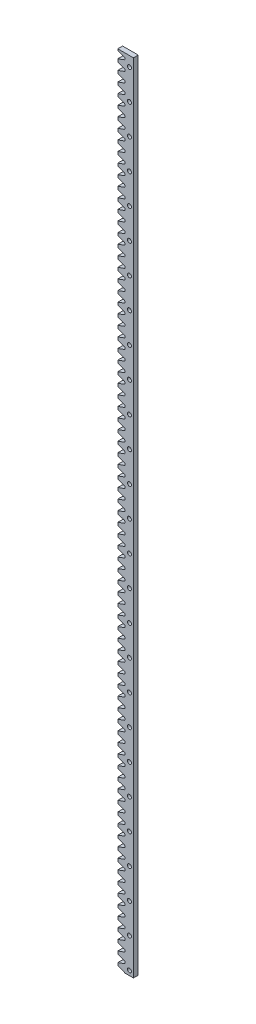
SolidWorks part; units mm, degrees
material "Thornel Mat VMA"
ref_plane "前视基准面" through (0, 0, 0) normal (0, 0, 1) x (1, 0, 0)
ref_plane "上视基准面" through (0, 0, 0) normal (0, 1, 0) x (1, 0, 0)
ref_plane "右视基准面" through (0, 0, 0) normal (1, 0, 0) x (0, 0, -1)
ref_axis "基准轴1" through (0, -55, 0) along (0, 1, 0)
sketch "SketchCI.m_strSketchName" plane through (0, 0, 0) normal (0, 0, 1) x (1, 0, 0)
  line L0 (-1.8, 3.1416) -> (-1.8, -719.4247)
  line L1 (-1.8, -719.4247) -> (19.05, -719.4247)
  line L2 (19.05, -719.4247) -> (19.05, 3.1416)
  line L3 (19.05, 3.1416) -> (-1.8, 3.1416)
extrude "拉伸CI" add sketch "SketchCI.m_strSketchName" along normal blind 1.5 and the other way blind 1.5
sketch "齿草图大直齿轮" plane through (0, 0, 0) normal (0, 0, 1) x (1, 0, 0)
  line L0 (-1.8, 2.2987) -> (-1.8, -2.2987)
  line L1 (-1.8, -2.2987) -> (2.3052, -0.8046)
  line L2 (2.7, -0.2407) -> (2.7, 0.2407)
  line L3 (2.3052, 0.8046) -> (-1.8, 2.2987)
  arc A0 (2.3052, -0.8046) -> (2.7, -0.2407) centre (2.1, -0.2407) ccw
  arc A1 (2.7, 0.2407) -> (2.3052, 0.8046) centre (2.1, 0.2407) ccw
  dimension "D1" = 1.2
  dimension "D2" = 1.2
  dimension "FLANKONEANGLE" = 70
  dimension "FLANKTWOANGLE" = 70
extrude "齿拉伸切除大直齿轮" cut sketch "齿草图大直齿轮" against normal blind 2.5 and the other way blind 2.5
pattern_linear "齿形大直齿轮" count 115 spacing 6.2832 along (0, -1, 0) of "齿拉伸切除大直齿轮"
sketch "辅助草图大直齿轮" plane through (0, 0, 0) normal (0, 0, 1) x (1, 0, 0)
  line L0 (0, 0) -> (0, -722.5663) construction
sketch "草图1" plane through (0, 0, 1.5) normal (0, 0, 1) x (1, 0, 0)
  line L0 (8, 0) -> (8, -495.8584)
  line L1 (19.05, 3.1416) -> (-1.8, 3.1416) construction
  line L2 (8, -495.8584) -> (-4, -495.8584)
  line L3 (-4, -495.8584) -> (-4, -720.4247)
  line L4 (-4, -720.4247) -> (21.05, -720.4247)
  line L5 (21.05, -720.4247) -> (21.05, 3.1416)
  line L6 (21.05, 3.1416) -> (8, 3.1416)
  line L7 (0, 0) -> (0, -722.5663) construction
  line L8 (19.05, -719.4247) -> (19.05, 3.1416) construction
  line L9 (-1.8, -719.4247) -> (19.05, -719.4247) construction
  line L11 (3.7, -495.8584) -> (8, -495.8584) construction
  line L12 (8, 0) -> (8, 3.1416)
  line L14 (8, 0) -> (-2.8, 0) construction
  line L15 (-2.8, 0) -> (-2.8, 3.1416) construction
  line L16 (-2.8, 3.1416) -> (8, 3.1416) construction
  line L17 (-1.8, 3.1416) -> (-1.8, 2.2987) construction
  dimension "D1" = 8
  dimension "D2" = 2
  dimension "D3" = 499
  dimension "D4" = 1
  dimension "D5" = 12
  dimension "D6" = 1
extrude "切除-拉伸1" cut sketch "草图1" against normal blind 10
sketch "草图3" plane through (0, 0, 1.5) normal (0, 0, 1) x (1, 0, 0)
  line L0 (5.5, 0) -> (5.5, -437.143) construction
  line L2 (-1.8, -3.1416) -> (5.5, -3.1416) construction
  line L3 (-1.8, -2.2987) -> (-1.8, -3.9844) construction
  line L4 (8, 3.1416) -> (8, -495.8584) construction
  circle A0 centre (5.5, -3.1416) radius 1.25
  circle A1 centre (5.5, -21.9816) radius 1.25
  circle A2 centre (5.5, -40.8216) radius 1.25
  circle A3 centre (5.5, -59.6616) radius 1.25
  circle A4 centre (5.5, -78.5016) radius 1.25
  circle A5 centre (5.5, -97.3416) radius 1.25
  circle A6 centre (5.5, -116.1816) radius 1.25
  circle A7 centre (5.5, -135.0216) radius 1.25
  circle A8 centre (5.5, -153.8616) radius 1.25
  circle A9 centre (5.5, -172.7016) radius 1.25
  circle A10 centre (5.5, -191.5416) radius 1.25
  circle A11 centre (5.5, -210.3816) radius 1.25
  circle A12 centre (5.5, -229.2216) radius 1.25
  circle A13 centre (5.5, -248.0616) radius 1.25
  circle A14 centre (5.5, -266.9016) radius 1.25
  circle A15 centre (5.5, -285.7416) radius 1.25
  circle A16 centre (5.5, -304.5816) radius 1.25
  circle A17 centre (5.5, -323.4216) radius 1.25
  circle A18 centre (5.5, -342.2616) radius 1.25
  circle A19 centre (5.5, -361.1016) radius 1.25
  circle A20 centre (5.5, -379.9416) radius 1.25
  circle A21 centre (5.5, -398.7816) radius 1.25
  circle A22 centre (5.5, -417.6216) radius 1.25
  circle A23 centre (5.5, -436.4616) radius 1.25
  circle A24 centre (5.5, -455.3016) radius 1.25
  circle A25 centre (5.5, -474.1416) radius 1.25
  circle A26 centre (5.5, -492.9816) radius 1.25
  dimension "D1" = 2.5
  dimension "D2" = 2.5
  dimension "D4" = 18.84
  dimension "D3" = 27
extrude "切除-拉伸2" cut sketch "草图3" against normal through all
sketch "草图4" plane through (0, 0, 1.5) normal (0, 0, 1) x (1, 0, 0)
  circle A0 centre (5.5, -3.1416) radius 2.5 construction
  dimension "D1" = 5
